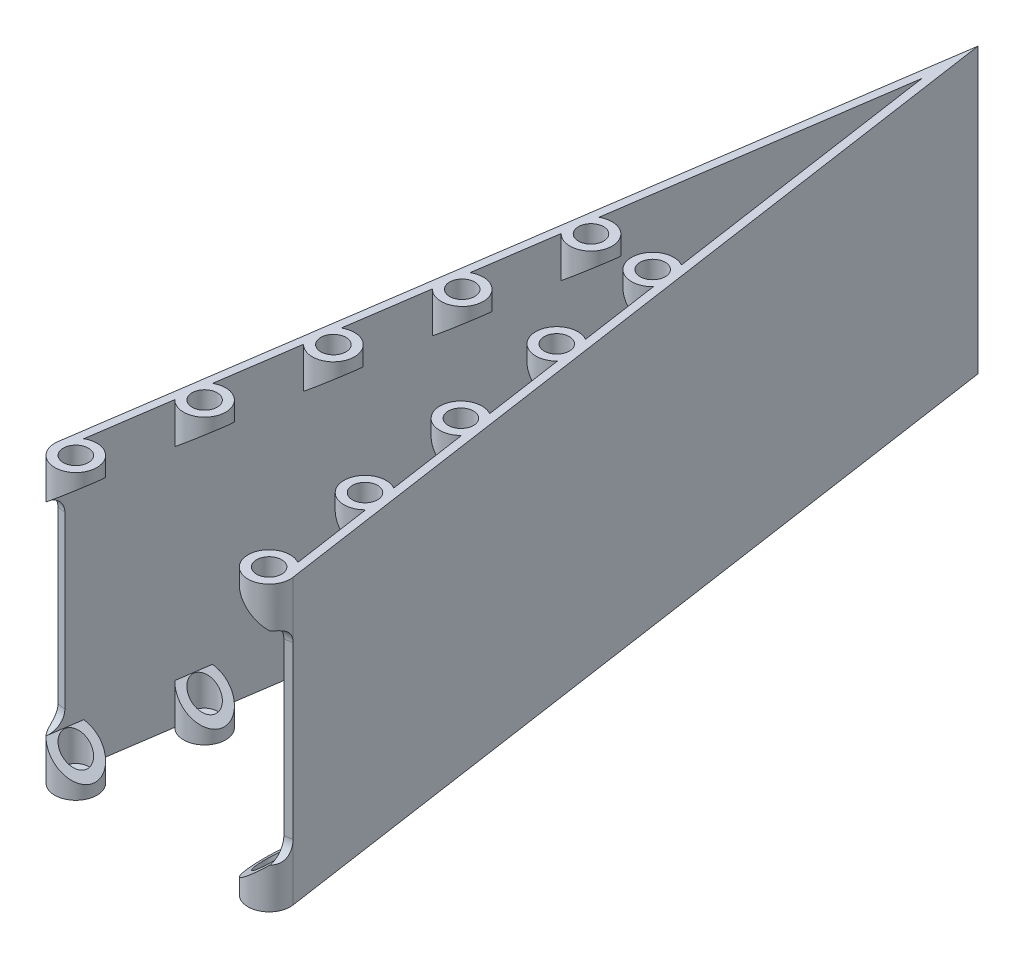
SolidWorks part; units mm, degrees
ref_plane "Front Plane" through (0, 0, 0) normal (0, 0, 1) x (1, 0, 0)
ref_plane "Top Plane" through (0, 0, 0) normal (0, 1, 0) x (1, 0, 0)
ref_plane "Right Plane" through (0, 0, 0) normal (1, 0, 0) x (0, 0, -1)
sketch "Sketch1" plane through (0, 0, 0) normal (0, 1, 0) x (1, 0, 0)
  line L0 (-13.5, 0) -> (13.5, 0) construction
  line L1 (-13.5, 0) -> (0, 92.188)
  line L2 (0, 92.188) -> (13.5, 0)
  line L3 (13.5, 0) -> (14.4894, 0.1449)
  line L4 (14.4894, 0.1449) -> (0, 99.0896)
  line L5 (0, 99.0896) -> (-14.4894, 0.1449)
  line L6 (-14.4894, 0.1449) -> (-13.5, 0)
  point P2 (0, 0)
  dimension "D1" = 90
  dimension "D2" = 90
  dimension "D4" = 1
  dimension "D3" = 100
  dimension "D5" = 27
extrude "Boss-Extrude1" add sketch "Sketch1" along normal blind 35
sketch "Sketch2" plane through (0, 0, 0) normal (0, 1, 0) x (1, 0, 0)
  line L0 (0, -1000) -> (0, 49000) construction
  line L1 (0, 92.188) -> (13.5, 0) construction
  line L2 (0, 92.188) -> (13.5, 0) construction
  line L3 (11.9169, -0.2318) -> (13.5, 0) construction
  line L4 (13.5, 0) -> (14.4894, 0.1449) construction
  line L5 (14.4894, 0.1449) -> (0, 99.0896) construction
  line L6 (14.4894, 0.1449) -> (0, 99.0896) construction
  circle A0 centre (11.9169, -0.2318) radius 2.6
  circle A1 centre (11.9169, -0.2318) radius 1.55
  circle A2 centre (9.8884, 13.6204) radius 1.55
  circle A3 centre (9.8884, 13.6204) radius 2.6
  circle A4 centre (7.8598, 27.4727) radius 1.55
  circle A5 centre (7.8598, 27.4727) radius 2.6
  circle A6 centre (5.8313, 41.3249) radius 1.55
  circle A7 centre (5.8313, 41.3249) radius 2.6
  circle A8 centre (3.8028, 55.1772) radius 1.55
  circle A9 centre (3.8028, 55.1772) radius 2.6
  circle A12 centre (-11.9169, -0.2318) radius 2.6
  circle A13 centre (-11.9169, -0.2318) radius 1.55
  circle A14 centre (-9.8884, 13.6204) radius 2.6
  circle A15 centre (-9.8884, 13.6204) radius 1.55
  circle A16 centre (-7.8598, 27.4727) radius 2.6
  circle A17 centre (-7.8598, 27.4727) radius 1.55
  circle A18 centre (-5.8313, 41.3249) radius 2.6
  circle A19 centre (-5.8313, 41.3249) radius 1.55
  circle A20 centre (-3.8028, 55.1772) radius 2.6
  circle A21 centre (-3.8028, 55.1772) radius 1.55
  dimension "D1" = 5.2
  dimension "D2" = 3.1
  dimension "D4" = 14
  dimension "D3" = 5
extrude "Boss-Extrude3" add sketch "Sketch2" along normal blind 5
sketch "Sketch4" plane through (0.2834, 0, 1.9354) normal (0.1449, 0, 0.9894) x (0.9894, 0, -0.1449)
  line L0 (9.1575, 5) -> (9.1575, 0) construction
  line L1 (14.3575, 5) -> (9.1575, 5) construction
  line L2 (13.3575, 35) -> (13.3575, 0) construction
  line L3 (9.1575, 5) -> (9.1575, 0) construction
  line L4 (14.3575, 5) -> (9.1575, 5) construction
  line L5 (13.3575, 35) -> (13.3575, 0) construction
  line L6 (13.3575, 5) -> (9.1575, 1.4758)
  line L7 (13.3575, 5) -> (9.1575, 5)
  line L8 (9.1575, 5) -> (9.1575, 1.4758)
  dimension "D1" = 40
extrude "Cut-Extrude1" cut sketch "Sketch4" against normal up to surface and the other way through all contours L7 L8 L6 region at (10.7295, 3.8253, 0.4057) up to face at (-8.5575, 5.4545, -33.751)
sketch "Sketch5" plane through (-0.2834, 0, 1.9354) normal (-0.1449, 0, 0.9894) x (0.9894, 0, 0.1449)
  line L0 (-9.1575, 0) -> (-9.1575, 5) construction
  line L1 (-9.1575, 5) -> (-14.3575, 5) construction
  line L2 (-13.3575, 35) -> (-13.3575, 0) construction
  line L3 (-9.1575, 0) -> (-9.1575, 5) construction
  line L4 (-9.1575, 5) -> (-14.3575, 5) construction
  line L5 (-13.3575, 35) -> (-13.3575, 0) construction
  line L6 (-13.3575, 5) -> (-9.1575, 1.4758)
  line L7 (-13.3575, 5) -> (-9.1575, 5)
  line L8 (-9.1575, 5) -> (-9.1575, 1.4758)
  dimension "D1" = 40
extrude "Cut-Extrude2" cut sketch "Sketch5" against normal up to surface and the other way through all contours L8 L7 L6 region at (-10.7295, 3.8253, 0.4057) up to face at (8.5575, 5.4545, -33.751)
ref_plane "Plane1" through (0, 17.5, 0) normal (0, 1, 0) x (1, 0, 0)
mirror "Mirror2" about plane through (0, 17.5, 0) normal (0, 1, 0) of "Cut-Extrude2", "Cut-Extrude1", "Boss-Extrude3"
fillet "Fillet1" radius 2 4 edges at (-13.9947, 5, -0.0724) (13.9947, 5, -0.0724) (13.9947, 30, -0.0724) (-13.9947, 30, -0.0724)
sketch "Sketch6" plane through (0, 0, 0) normal (0, -1, 0) x (1, 0, 0)
  arc A0 (-13.2031, -2.0278) -> (-14.4894, -0.1449) centre (-11.9169, 0.2318) ccw construction
  arc A1 (14.4894, -0.1449) -> (13.2031, -2.0278) centre (11.9169, 0.2318) ccw construction
  arc A2 (11.7684, -11.8245) -> (11.1745, -15.88) centre (9.8884, -13.6204) ccw construction
  arc A3 (-11.1745, -15.88) -> (-11.7684, -11.8245) centre (-9.8884, -13.6204) ccw construction
  arc A4 (-9.146, -29.7323) -> (-9.7399, -25.6768) centre (-7.8598, -27.4727) ccw construction
  arc A5 (9.7399, -25.6768) -> (9.146, -29.7323) centre (7.8598, -27.4727) ccw construction
  arc A6 (7.7114, -39.529) -> (7.1175, -43.5845) centre (5.8313, -41.3249) ccw construction
  arc A7 (-7.1175, -43.5845) -> (-7.7114, -39.529) centre (-5.8313, -41.3249) ccw construction
  arc A8 (-5.089, -57.4368) -> (-5.6829, -53.3813) centre (-3.8028, -55.1772) ccw construction
  arc A9 (5.6829, -53.3813) -> (5.089, -57.4368) centre (3.8028, -55.1772) ccw construction
  arc A10 (-13.2031, -2.0278) -> (-14.4894, -0.1449) centre (-11.9169, 0.2318) ccw
  arc A11 (14.4894, -0.1449) -> (13.2031, -2.0278) centre (11.9169, 0.2318) ccw
  arc A12 (11.7684, -11.8245) -> (11.1745, -15.88) centre (9.8884, -13.6204) ccw
  arc A13 (-11.1745, -15.88) -> (-11.7684, -11.8245) centre (-9.8884, -13.6204) ccw
  arc A14 (-9.146, -29.7323) -> (-9.7399, -25.6768) centre (-7.8598, -27.4727) ccw
  arc A15 (9.7399, -25.6768) -> (9.146, -29.7323) centre (7.8598, -27.4727) ccw
  arc A16 (7.7114, -39.529) -> (7.1175, -43.5845) centre (5.8313, -41.3249) ccw
  arc A17 (-7.1175, -43.5845) -> (-7.7114, -39.529) centre (-5.8313, -41.3249) ccw
  arc A18 (-5.089, -57.4368) -> (-5.6829, -53.3813) centre (-3.8028, -55.1772) ccw
  arc A19 (5.6829, -53.3813) -> (5.089, -57.4368) centre (3.8028, -55.1772) ccw
  circle A20 centre (3.8028, -55.1772) radius 2.6
  circle A21 centre (-3.8028, -55.1772) radius 2.6
  circle A22 centre (5.8313, -41.3249) radius 2.6
  circle A23 centre (-5.8313, -41.3249) radius 2.6
  circle A24 centre (7.8598, -27.4727) radius 2.6
  circle A25 centre (-7.8598, -27.4727) radius 2.6
  circle A26 centre (-9.8884, -13.6204) radius 2.6
  circle A27 centre (9.8884, -13.6204) radius 2.6
  circle A28 centre (11.9169, 0.2318) radius 2.6
  circle A29 centre (-11.9169, 0.2318) radius 2.6
  circle M23 centre (11.9169, 0.2318) radius 1.55
  circle M24 centre (9.8884, -13.6204) radius 1.55
  circle M25 centre (7.8598, -27.4727) radius 1.55
  circle M26 centre (5.8313, -41.3249) radius 1.55
  circle M27 centre (3.8028, -55.1772) radius 1.55
  circle M28 centre (-5.8313, -41.3249) radius 1.55
  circle M29 centre (-9.8884, -13.6204) radius 1.55
  circle M30 centre (-11.9169, 0.2318) radius 1.55
  circle M31 centre (-7.8598, -27.4727) radius 1.55
  circle M32 centre (-3.8028, -55.1772) radius 1.55
extrude "Boss-Extrude4" add sketch "Sketch6" against normal blind 1 contours M27 | M32 | M28 | M26 | M25 | M31 | M29 | M24 | M23 | M30 region at (11.9169, 0, 0.2318) region at (9.8884, 0, -13.6204) region at (7.8598, 0, -27.4727) region at (5.8313, 0, -41.3249) region at (3.8028, 0, -55.1772) region at (-5.8313, 0, -41.3249) region at (-9.8884, 0, -13.6204) region at (-11.9169, 0, 0.2318) region at (-7.8598, 0, -27.4727) region at (-3.8028, 0, -55.1772)
equation "\"D2@Sketch1\"=\"D1@Sketch1\""
